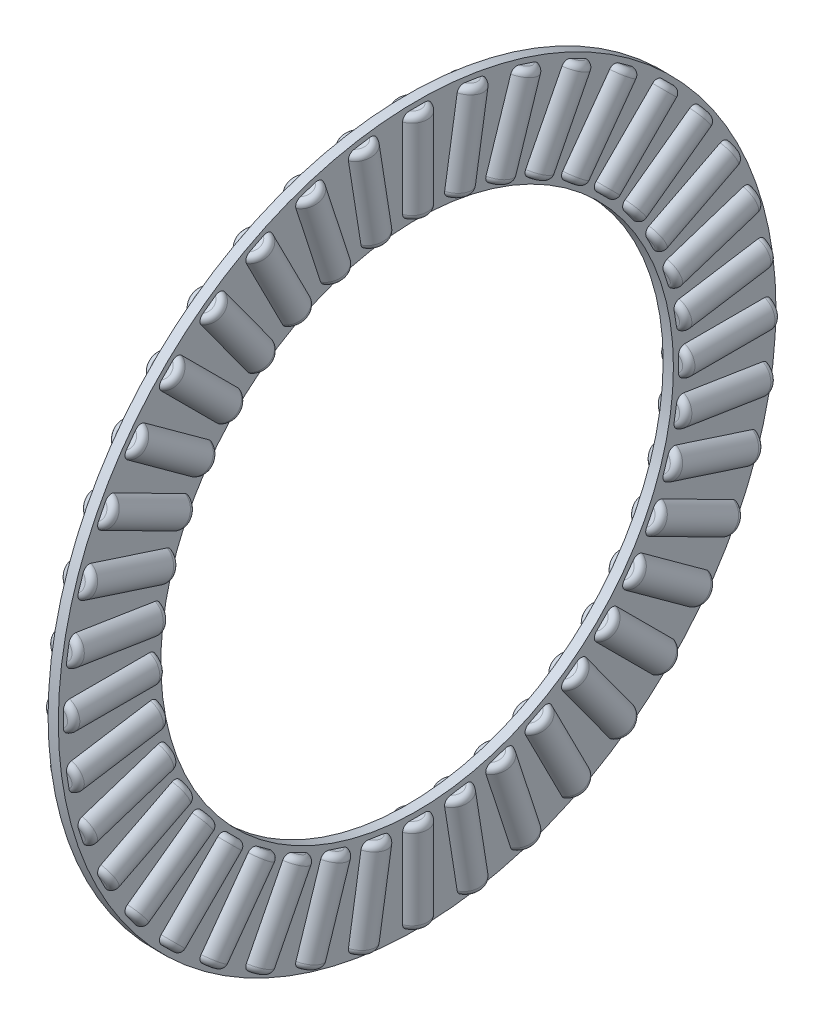
SolidWorks part; units mm, degrees
ref_plane "Plane1" through (0, 0, 0) normal (0, 0, 1) x (1, 0, 0)
ref_plane "Plane2" through (0, 0, 0) normal (0, 1, 0) x (1, 0, 0)
ref_plane "Plane3" through (0, 0, 0) normal (1, 0, 0) x (0, 0, -1)
sketch "Clipboard" plane through (0, 0, 0) normal (0, 0, 1) x (1, 0, 0)
  line L0 (-10, 0) -> (10, 0) construction
  line L1 (0, 0) -> (17.1293, -14.3732)
  line L2 (0, 0) -> (22.9813, 19.2836)
  line L3 (0, 0) -> (17.1293, -14.3732)
  line L4 (0, 0) -> (-22.3471, -0.7804)
  dimension "BallCLRad" = 30
sketch "CagSpiSke" plane through (0, 0, 0) normal (0, 0, 1) x (1, 0, 0)
  line L5 (-34.925, 0) -> (34.925, 0) construction
  line L6 (-0.5, 35) -> (0.5, 35)
  line L7 (-0.5, 35) -> (-0.5, 25)
  line L8 (-0.5, 25) -> (0.5, 25)
  line L9 (0.5, 35) -> (0.5, 25)
  dimension "ID" = 50
  dimension "OD" = 70
revolve "CageSpine" add sketch "CagSpiSke" angle 360 about L5 reverse direction yes
ref_axis "Axis1" through (-50, 0, 0) along (1, 0, 0)
sketch "RolDetSke" plane through (0, 0, 0) normal (0, 0, 1) x (1, 0, 0)
  line L0 (0, 33.02) -> (0, 55.88) construction
  line L3 (0, 34.5) -> (0.9, 34.5)
  line L4 (0, 34.5) -> (0, 25.5)
  line L5 (0, 25.5) -> (0.9, 25.5)
  line L6 (1.5, 33.9) -> (1.5, 26.1)
  arc A0 (1.5, 26.1) -> (0.9, 25.5) centre (0.9, 26.1) cw
  arc A1 (0.9, 34.5) -> (1.5, 33.9) centre (0.9, 33.9) cw
  dimension "Roller_diameter" = 3
  dimension "Cyl_Len" = 9
  dimension "offset" = 25.5
revolve "RollerDetailed" add sketch "RolDetSke" angle 360 about L0 reverse direction yes
pattern_circular "RollersDetailed" count 40 every 9 about axis through (-50, 0, 0) along (1, 0, 0) of "RollerDetailed"
sketch "RolSimSke" plane through (0, 0, 0) normal (0, 0, 1) x (1, 0, 0)
  line L1 (-17.78, 0) -> (12.7, 0) construction
  line L3 (-0.9, 36.075) -> (0.9, 36.075)
  line L4 (-1.5, 35.475) -> (-1.5, 27.675)
  line L5 (-0.9, 27.075) -> (0.9, 27.075)
  line L6 (1.5, 35.475) -> (1.5, 27.675)
  arc A0 (-1.5, 27.675) -> (-0.9, 27.075) centre (-0.9, 27.675) ccw
  arc A1 (-0.9, 36.075) -> (-1.5, 35.475) centre (-0.9, 35.475) ccw
  arc A2 (1.5, 35.475) -> (0.9, 36.075) centre (0.9, 35.475) ccw
  arc A3 (0.9, 27.075) -> (1.5, 27.675) centre (0.9, 27.675) ccw
  dimension "Halfdia" = 1.5
  dimension "Roller_diameter" = 3
  dimension "Cyl_Len" = 9
  dimension "offset" = 25.5
revolve "RollersSimplified" [suppressed] add sketch "RolSimSke" angle 360 about L1
equation "\"BallCLRad@Clipboard\" =  ( \"OD@CagSpiSke\" + \"ID@CagSpiSke\" )  / 4"
equation "\"offset@RolSimSke\" = \"BallCLRad@Clipboard\" - \"Cyl_Len@RolSimSke\" / 2"
equation "\"offset@RolDetSke\" = \"BallCLRad@Clipboard\" - \"Cyl_Len@RolDetSke\" / 2"
equation "\"Thickness@CagSpiSke\" =  \"Roller_diameter@RolDetSke\"  / 3"
equation "\"HalfThick@CagSpiSke\" = \"Thickness@CagSpiSke\" / 2"
equation "\"radius@RolDetSke\" =  ( \"Roller_diameter@RolDetSke\" - \"Thickness@CagSpiSke\" )  * 0.6 / 2"
equation "\"Roller_diameter@RolSimSke\" = \"Roller_diameter@RolDetSke\""
equation "\"Cyl_Len@RolSimSke\" = \"Cyl_Len@RolDetSke\""
equation "\"Rol_rad@RolSimSke\" = \"radius@RolDetSke\""
equation "\"Halfdia@RolSimSke\" = \"Roller_diameter@RolSimSke\" / 2"
equation "\"Max_count@Clipboard\" = int( 3.14159265 / atn(( \"Roller_diameter@RolDetSke\" / 2) / sqr( \"offset@RolDetSke\"  *  \"offset@RolDetSke\" - ( \"Roller_diameter@RolDetSke\" / 2) *  ( \"Roller_diameter@RolDetSke\" / 2))))"
equation "\"Max_count@Clipboard\" = ((sgn( \"Max_count@Clipboard\" - \"Count@Clipboard\" )-1)*( \"Max_count@Clipboard\" - \"Count@Clipboard\" ))/-2+ \"Count@Clipboard\""
equation "\"Count@RollersDetailed\" = int( \"Show_count@Clipboard\" ) "
equation "\"Count@RollersDetailed\" = ((sgn( \"Count@RollersDetailed\" - \"Max_count@Clipboard\" )-1)*( \"Count@RollersDetailed\" - \"Max_count@Clipboard\" ))/-2+ \"Max_count@Clipboard\""
equation "\"Count@RollersDetailed\" = ((sgn( \"Count@RollersDetailed\" - \"Min_count@Clipboard\" )+1)*( \"Count@RollersDetailed\" - \"Min_count@Clipboard\"))/2 +\"Min_count@Clipboard\""
equation "\"Angle@RollersDetailed\" = 360.0 / \"Max_count@Clipboard\""
